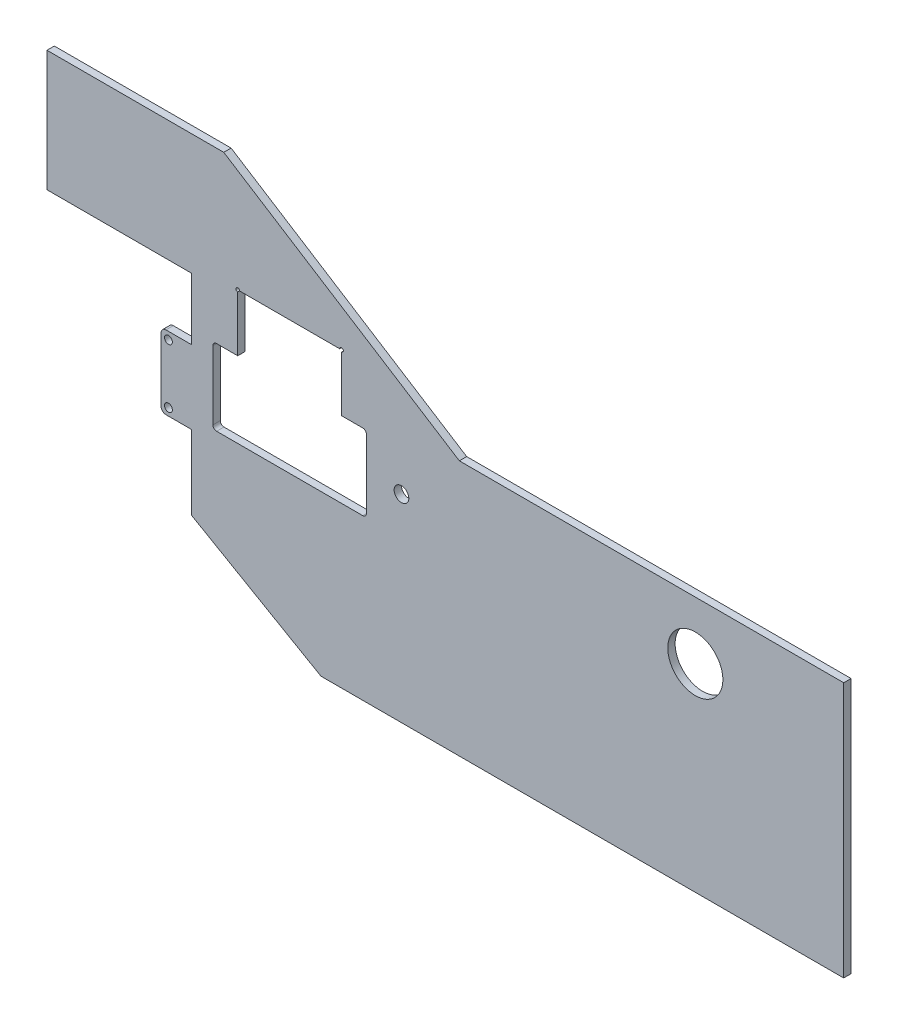
SolidWorks part; units mm, degrees
material "Thornel Mat VMA"
ref_plane "Front Plane" through (0, 0, 0) normal (0, 0, 1) x (1, 0, 0)
ref_plane "Top Plane" through (0, 0, 0) normal (0, 1, 0) x (1, 0, 0)
ref_plane "Right Plane" through (0, 0, 0) normal (1, 0, 0) x (0, 0, -1)
sketch "Sketch1" plane through (0, 0, 0) normal (0, 0, 1) x (1, 0, 0)
  line L1 (20.2869, 47.6) -> (204.7012, 47.6)
  line L2 (20.2869, 47.6) -> (20.2869, -36.0143)
  line L3 (20.2869, -36.0143) -> (204.7012, -36.0143)
  line L4 (204.7012, 47.6) -> (204.7012, -36.0143)
extrude "Boss-Extrude1" add sketch "Sketch1" along normal blind 3
sketch "Sketch2" plane through (0, 0, 0) normal (0, 0, -1) x (-1, 0, 0)
  circle A0 centre (-24.1169, 24) radius 3
  dimension "D1" = 6
extrude "Cut-Extrude1" cut sketch "Sketch2" against normal blind 70
sketch "Sketch3" plane through (0, 0, 3) normal (0, 0, 1) x (1, 0, 0)
  line L0 (24.1169, 24) -> (144.1169, 24) construction
  circle A0 centre (144.1169, 24) radius 11.25
  dimension "D2" = 22.5
  dimension "D1" = 120
extrude "Cut-Extrude2" cut sketch "Sketch3" against normal blind 3
sketch "Sketch4" plane through (0, 0, 3) normal (0, 0, 1) x (1, 0, 0)
  line L0 (-61.5431, 47.6) -> (-61.5431, -3) construction
  line L1 (-61.5431, 59.2602) -> (-61.5431, 34)
  line L2 (-61.5431, 4) -> (-61.5431, -26.3865)
  line L3 (-61.5431, 34) -> (-72.0431, 34)
  line L5 (-61.5431, 4) -> (-72.0431, 4)
  line L6 (-74.0431, 32) -> (-74.0431, 6)
  line L7 (-48.4526, 108.6033) -> (-120.6472, 108.6033)
  line L8 (-120.6472, 108.6033) -> (-120.6472, 59.2602)
  line L9 (-120.6472, 59.2602) -> (-61.5431, 59.2602)
  line L10 (-48.4526, 108.6033) -> (47.7584, 47.6)
  line L11 (20.2869, 47.6) -> (20.2869, -36.0143)
  line L12 (20.2869, -36.0143) -> (204.7012, -36.0143)
  line L13 (204.7012, -36.0143) -> (204.7012, 47.6)
  line L14 (204.7012, 47.6) -> (20.2869, 47.6)
  line L15 (20.2869, 47.6) -> (20.2869, -36.0143)
  line L16 (20.2869, -36.0143) -> (204.7012, -36.0143)
  line L18 (47.7584, 47.6) -> (20.2869, 47.6)
  line L19 (-61.5431, -26.3865) -> (-8.7573, -56.8219)
  line L20 (-8.7573, -56.8219) -> (204.7012, -56.8219)
  line L21 (204.7012, -56.8219) -> (204.7012, -36.0143)
  circle A0 centre (-71.0431, 31) radius 1.6
  circle A1 centre (-71.0431, 7) radius 1.6
  arc A2 (-72.0431, 4) -> (-74.0431, 6) centre (-72.0431, 6) cw
  arc A3 (-72.0431, 34) -> (-74.0431, 32) centre (-72.0431, 32) ccw
  dimension "D1" = 3.2
  dimension "D2" = 3
  dimension "D5" = 2
  dimension "D3" = 3
  dimension "D4" = 3
  dimension "D6" = 0
extrude "Boss-Extrude2" add sketch "Sketch4" against normal blind 3
sketch "Sketch5" plane through (0, 0, 3) normal (0, 0, 1) x (1, 0, 0)
  line L0 (-0.5431, 62.6) -> (-42.5431, 62.6) construction
  line L1 (8.2869, 8.5) -> (-51.3731, 8.5)
  line L2 (9.7869, 10) -> (9.7869, 38)
  line L3 (8.2869, 39.5) -> (-51.3731, 39.5)
  line L4 (-52.8731, 10) -> (-52.8731, 38)
  line L5 (-41.9931, 62.8) -> (-1.0931, 62.8)
  line L6 (-42.7431, 62.05) -> (-42.7431, 39.5)
  line L7 (-42.7431, 39.5) -> (-0.3431, 39.5)
  line L8 (-0.3431, 62.05) -> (-0.3431, 39.5)
  line L9 (-42.5431, 57.6) -> (-42.5431, 52.6) construction
  line L10 (-0.5431, 62.6) -> (-0.5431, 57.6) construction
  line L13 (7.7869, 47.6) -> (7.7869, -3) construction
  line L14 (-50.8731, -3) -> (-50.8731, 47.6) construction
  line L15 (8.4569, 34.5) -> (-51.5431, 34.5) construction
  line L16 (-51.5431, 13.5) -> (8.4569, 13.5) construction
  arc A0 (9.7869, 38) -> (8.2869, 39.5) centre (8.2869, 38) ccw
  arc A1 (8.2869, 8.5) -> (9.7869, 10) centre (8.2869, 10) ccw
  arc A2 (-51.3731, 8.5) -> (-52.8731, 10) centre (-51.3731, 10) cw
  arc A3 (-51.3731, 39.5) -> (-52.8731, 38) centre (-51.3731, 38) ccw
  arc A4 (-41.9931, 62.8) -> (-42.7431, 62.05) centre (-42.7431, 62.8) ccw
  arc A5 (-0.3431, 62.05) -> (-1.0931, 62.8) centre (-0.3431, 62.8) ccw
  dimension "D8" = 1.5
  dimension "D9" = 1.5
  dimension "D1" = 0.2
  dimension "D2" = 0.2
  dimension "D3" = 0.2
  dimension "D4" = 2
  dimension "D5" = 2
  dimension "D6" = 5
  dimension "D7" = 5
extrude "Cut-Extrude3" cut sketch "Sketch5" against normal blind 10 contours L8 L5 L6 L3 | L4 L1 L2 L3 region at (-21.5431, 24, 3) region at (-21.5431, 51.1815, 3)
